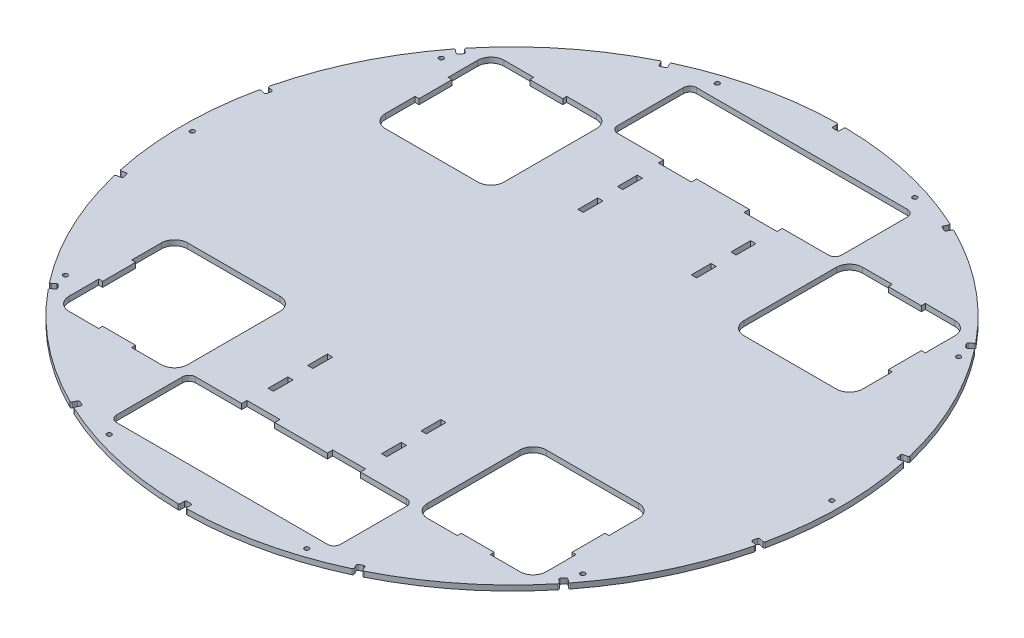
SolidWorks part; units mm, degrees
ref_plane "Front Plane" through (0, 0, 0) normal (0, 0, 1) x (1, 0, 0)
ref_plane "Top Plane" through (0, 0, 0) normal (0, 1, 0) x (1, 0, 0)
ref_plane "Right Plane" through (0, 0, 0) normal (1, 0, 0) x (0, 0, -1)
sketch "Sketch1" plane through (0, 0, 0) normal (0, 1, 0) x (1, 0, 0)
  circle A0 centre (0, 0) radius 250
extrude "Boss-Extrude1" add sketch "Sketch1" along normal blind 4
sketch "Sketch2" plane through (0, 4, 0) normal (0, 1, 0) x (1, 0, 0)
  line L0 (0, -250) -> (0, 250) construction
  line L1 (80, 220) -> (-80, 220)
  line L2 (85, 215) -> (85, 165)
  line L3 (80, 160) -> (-80, 160)
  line L4 (-85, 215) -> (-85, 165)
  line L5 (85, 220) -> (-85, 160) construction
  line L6 (85, 160) -> (-85, 220) construction
  line L7 (-55, 0) -> (55, 0) construction
  line L8 (85, -215) -> (85, -165)
  line L9 (80, -160) -> (-80, -160)
  line L10 (-85, -215) -> (-85, -165)
  line L11 (80, -220) -> (-80, -220)
  circle A0 centre (0, 0) radius 250 construction
  arc A1 (-80, 160) -> (-85, 165) centre (-80, 165) cw
  arc A2 (80, 160) -> (85, 165) centre (80, 165) ccw
  arc A3 (85, 215) -> (80, 220) centre (80, 215) ccw
  arc A4 (-80, 220) -> (-85, 215) centre (-80, 215) ccw
  arc A5 (-85, -215) -> (-80, -220) centre (-80, -215) ccw
  arc A6 (80, -220) -> (85, -215) centre (80, -215) ccw
  arc A7 (85, -165) -> (80, -160) centre (80, -165) ccw
  arc A8 (-80, -160) -> (-85, -165) centre (-80, -165) ccw
  point P0 (0, 190)
  point P33 (-85, -220)
  point P36 (85, -220)
  point P39 (85, -160)
  point P42 (-85, -160)
  dimension "D4" = 5
  dimension "D5" = 5
  dimension "D1" = 170
  dimension "D2" = 190
  dimension "D3" = 60
extrude "Cut-Extrude1" cut sketch "Sketch2" against normal blind 10
sketch "Sketch3" plane through (0, 4, 0) normal (0, 1, 0) x (1, 0, 0)
  line L0 (45, 160) -> (-45, 160)
  line L1 (-80, 160) -> (80, 160) construction
  line L2 (0, -2.2) -> (0, 2.2) construction
  line L3 (-45, 160) -> (-20, 160)
  line L4 (-45, 160) -> (-45, 156)
  line L5 (-45, 156) -> (-20, 156)
  line L6 (-20, 160) -> (-20, 156)
  line L7 (20, 160) -> (20, 156)
  line L8 (45, 156) -> (20, 156)
  line L9 (45, 160) -> (45, 156)
  line L10 (45, 160) -> (20, 160)
  line L11 (-2.2, 0) -> (2.2, 0) construction
  line L12 (45, -160) -> (20, -160)
  line L13 (45, -160) -> (45, -156)
  line L14 (45, -156) -> (20, -156)
  line L15 (20, -160) -> (20, -156)
  line L16 (-20, -160) -> (-20, -156)
  line L17 (-45, -156) -> (-20, -156)
  line L18 (-45, -160) -> (-45, -156)
  line L19 (-45, -160) -> (-20, -160)
  line L20 (45, -160) -> (-45, -160)
  point P5 (0, 160)
  point P24 (0, -160)
  line M7 (80, 160) -> (-80, 160)
  line M10 (-80, -160) -> (80, -160)
  dimension "D2" = 4
  dimension "D3" = 25
extrude "Cut-Extrude2" cut sketch "Sketch3" against normal blind 5 contours L6 L0 L4 L5 | L9 L7 L8 M7 | L18 L16 L17 M10 | L15 L13 L14 M10 region at (32.5, 4, -158) region at (-32.5, 4, -158) region at (-32.5, 4, 158) region at (32.5, 4, 158)
sketch "Sketch4" plane through (0, 4, 0) normal (0, 1, 0) x (1, 0, 0)
  line L0 (45, 160) -> (-45, 160)
  line L3 (80, 220) -> (-80, 220) construction
  line L4 (45, 160) -> (80, 160) construction
  line L5 (45, 140) -> (41, 140)
  line L6 (45, 140) -> (45, 125)
  line L7 (45, 125) -> (41, 125)
  line L8 (41, 140) -> (41, 125)
  line L9 (0, -2.2) -> (0, 2.2) construction
  line L10 (41, 110) -> (45, 110)
  line L11 (41, 110) -> (41, 95)
  line L12 (41, 95) -> (45, 95)
  line L13 (45, 110) -> (45, 95)
  line L14 (-45, 110) -> (-45, 95)
  line L15 (-41, 95) -> (-45, 95)
  line L16 (-41, 110) -> (-41, 95)
  line L17 (-41, 110) -> (-45, 110)
  line L18 (-41, 140) -> (-41, 125)
  line L19 (-45, 125) -> (-41, 125)
  line L20 (-45, 140) -> (-45, 125)
  line L21 (-45, 140) -> (-41, 140)
  line L22 (-2.2, 0) -> (2.2, 0) construction
  line L23 (-45, -140) -> (-41, -140)
  line L24 (-45, -140) -> (-45, -125)
  line L25 (-45, -125) -> (-41, -125)
  line L26 (-41, -140) -> (-41, -125)
  line L27 (-41, -110) -> (-45, -110)
  line L28 (-41, -110) -> (-41, -95)
  line L29 (-41, -95) -> (-45, -95)
  line L30 (-45, -110) -> (-45, -95)
  line L31 (45, -110) -> (45, -95)
  line L32 (41, -95) -> (45, -95)
  line L33 (41, -110) -> (41, -95)
  line L34 (41, -110) -> (45, -110)
  line L35 (41, -140) -> (41, -125)
  line L36 (45, -125) -> (41, -125)
  line L37 (45, -140) -> (45, -125)
  line L38 (45, -140) -> (41, -140)
  point P3 (0, 160)
  point P5 (0, 220)
  point P16 (45, 132.5)
  point P17 (45, 102.5)
  dimension "D1" = 0
  dimension "D2" = 4
  dimension "D3" = 0
  dimension "D4" = 90
  dimension "D5" = 15
  dimension "D6" = 20
  dimension "D7" = 15
  dimension "D8" = 4
  dimension "D9" = 30
extrude "Cut-Extrude3" cut sketch "Sketch4" against normal blind 20 contours L5 L8 L7 L6 | L13 L10 L11 L12 | L21 L20 L19 L18 | L16 L17 L14 L15 | L30 L27 L28 L29 | L23 L26 L25 L24 | L33 L34 L31 L32 | L38 L37 L36 L35 region at (43, 4, -132.5) region at (43, 4, -102.5) region at (-43, 4, -102.5) region at (-43, 4, -132.5) region at (-43, 4, 132.5) region at (-43, 4, 102.5) region at (43, 4, 102.5) region at (43, 4, 132.5)
sketch "Sketch7" plane through (0, 4, 0) normal (0, 1, 0) x (1, 0, 0)
  line L0 (0, -2.2) -> (0, 2.2) construction
  line L1 (-101, 75) -> (-171, 75)
  line L2 (-91, 85) -> (-91, 155)
  line L3 (-101, 165) -> (-171, 165)
  line L4 (-181, 85) -> (-181, 155)
  line L5 (-91, 75) -> (-181, 165) construction
  line L6 (-91, 165) -> (-181, 75) construction
  line L7 (91, 165) -> (181, 75) construction
  line L8 (91, 75) -> (181, 165) construction
  line L9 (181, 85) -> (181, 155)
  line L10 (101, 165) -> (171, 165)
  line L11 (91, 85) -> (91, 155)
  line L12 (101, 75) -> (171, 75)
  line L13 (-2.2, 0) -> (2.2, 0) construction
  line L14 (91, -75) -> (181, -165) construction
  line L15 (91, -165) -> (181, -75) construction
  line L16 (101, -75) -> (171, -75)
  line L17 (91, -85) -> (91, -155)
  line L18 (101, -165) -> (171, -165)
  line L19 (181, -85) -> (181, -155)
  line L20 (-91, -165) -> (-181, -75) construction
  line L21 (-91, -75) -> (-181, -165) construction
  line L22 (-181, -85) -> (-181, -155)
  line L23 (-101, -165) -> (-171, -165)
  line L24 (-91, -85) -> (-91, -155)
  line L25 (-101, -75) -> (-171, -75)
  arc A0 (-171, 165) -> (-181, 155) centre (-171, 155) ccw
  arc A1 (-91, 155) -> (-101, 165) centre (-101, 155) ccw
  arc A2 (-181, -155) -> (-171, -165) centre (-171, -155) ccw
  arc A3 (-101, -165) -> (-91, -155) centre (-101, -155) ccw
  arc A4 (-91, -85) -> (-101, -75) centre (-101, -85) ccw
  arc A5 (-171, -75) -> (-181, -85) centre (-171, -85) ccw
  arc A6 (91, -155) -> (101, -165) centre (101, -155) ccw
  arc A7 (171, -165) -> (181, -155) centre (171, -155) ccw
  arc A8 (181, -85) -> (171, -75) centre (171, -85) ccw
  arc A9 (101, -75) -> (91, -85) centre (101, -85) ccw
  arc A10 (101, 75) -> (91, 85) centre (101, 85) cw
  arc A11 (171, 75) -> (181, 85) centre (171, 85) ccw
  arc A12 (181, 155) -> (171, 165) centre (171, 155) ccw
  arc A13 (91, 155) -> (101, 165) centre (101, 155) cw
  arc A14 (-171, 75) -> (-181, 85) centre (-171, 85) cw
  arc A15 (-101, 75) -> (-91, 85) centre (-101, 85) ccw
  point P0 (-136, 120)
  point P12 (136, 120)
  point P19 (136, -120)
  point P24 (-136, -120)
  dimension "D5" = 10
  dimension "D6" = 10
  dimension "D7" = 10
  dimension "D1" = 90
  dimension "D2" = 90
  dimension "D3" = 136
  dimension "D4" = 120
extrude "Cut-Extrude4" cut sketch "Sketch7" against normal blind 5
sketch "Sketch8" plane through (0, 4, 0) normal (0, 1, 0) x (1, 0, 0)
  line L0 (-181, 155) -> (-181, 85) construction
  line L1 (-178, 107.5) -> (-184, 107.5)
  line L2 (-178, 107.5) -> (-178, 132.5)
  line L3 (-178, 132.5) -> (-184, 132.5)
  line L4 (-184, 107.5) -> (-184, 132.5)
  line L5 (-178, 107.5) -> (-184, 132.5) construction
  line L6 (-178, 132.5) -> (-184, 107.5) construction
  line L7 (-101, 165) -> (-171, 165) construction
  line L8 (-123.5, 162) -> (-148.5, 162)
  line L9 (-123.5, 162) -> (-123.5, 168)
  line L10 (-123.5, 168) -> (-148.5, 168)
  line L11 (-148.5, 162) -> (-148.5, 168)
  line L12 (-123.5, 162) -> (-148.5, 168) construction
  line L13 (-123.5, 168) -> (-148.5, 162) construction
  line L14 (0, -2.2) -> (0, 2.2) construction
  line L15 (123.5, 168) -> (148.5, 162) construction
  line L16 (123.5, 162) -> (148.5, 168) construction
  line L17 (178, 132.5) -> (184, 107.5) construction
  line L18 (178, 107.5) -> (184, 132.5) construction
  line L19 (148.5, 162) -> (148.5, 168)
  line L20 (123.5, 168) -> (148.5, 168)
  line L21 (123.5, 162) -> (123.5, 168)
  line L22 (123.5, 162) -> (148.5, 162)
  line L23 (184, 107.5) -> (184, 132.5)
  line L24 (178, 132.5) -> (184, 132.5)
  line L25 (178, 107.5) -> (178, 132.5)
  line L26 (178, 107.5) -> (184, 107.5)
  line L27 (-2.2, 0) -> (2.2, 0) construction
  line L28 (178, -107.5) -> (184, -132.5) construction
  line L29 (178, -132.5) -> (184, -107.5) construction
  line L30 (123.5, -162) -> (148.5, -168) construction
  line L31 (123.5, -168) -> (148.5, -162) construction
  line L32 (178, -107.5) -> (184, -107.5)
  line L33 (178, -107.5) -> (178, -132.5)
  line L34 (178, -132.5) -> (184, -132.5)
  line L35 (184, -107.5) -> (184, -132.5)
  line L36 (123.5, -162) -> (148.5, -162)
  line L37 (123.5, -162) -> (123.5, -168)
  line L38 (123.5, -168) -> (148.5, -168)
  line L39 (148.5, -162) -> (148.5, -168)
  line L40 (-123.5, -168) -> (-148.5, -162) construction
  line L41 (-123.5, -162) -> (-148.5, -168) construction
  line L42 (-178, -132.5) -> (-184, -107.5) construction
  line L43 (-178, -107.5) -> (-184, -132.5) construction
  line L44 (-148.5, -162) -> (-148.5, -168)
  line L45 (-123.5, -168) -> (-148.5, -168)
  line L46 (-123.5, -162) -> (-123.5, -168)
  line L47 (-123.5, -162) -> (-148.5, -162)
  line L48 (-184, -107.5) -> (-184, -132.5)
  line L49 (-178, -132.5) -> (-184, -132.5)
  line L50 (-178, -107.5) -> (-178, -132.5)
  line L51 (-178, -107.5) -> (-184, -107.5)
  point P0 (-181, 120)
  point P7 (-136, 165)
  point P24 (136, 165)
  point P25 (181, 120)
  point P36 (181, -120)
  point P37 (136, -165)
  point P46 (-136, -165)
  point P47 (-181, -120)
  dimension "D1" = 6
  dimension "D2" = 25
  dimension "D3" = 6
  dimension "D4" = 25
extrude "Boss-Extrude2" add sketch "Sketch8" against normal blind 4
sketch "Sketch11" plane through (0, 4, 0) normal (0, 1, 0) x (1, 0, 0)
  line L1 (1.5, 245) -> (-1.5, 245)
  line L2 (2.5, 246) -> (2.5, 255)
  line L3 (2.5, 255) -> (-2.5, 255)
  line L4 (-2.5, 246) -> (-2.5, 255)
  line L5 (2.5, 245) -> (-2.5, 255) construction
  line L6 (2.5, 255) -> (-2.5, 245) construction
  circle A0 centre (0, 0) radius 250 construction
  arc A1 (2.5, 246) -> (1.5, 245) centre (1.5, 246) cw
  arc A2 (-1.5, 245) -> (-2.5, 246) centre (-1.5, 246) cw
  point P0 (0, 250)
  dimension "D3" = 1
  dimension "D1" = 10
  dimension "D2" = 5
extrude "Cut-Extrude5" cut sketch "Sketch11" against normal blind 4
fillet "Fillet1" radius 1 2 edges at (2.5, 2, -249.9875) (-2.5, 2, -249.9875)
pattern_circular "CirPattern1" count 14 over 360 about axis through (0, 4, 0) along (0, -1, 0) of "Cut-Extrude5", "Fillet1"
sketch "Sketch12" plane through (0, 4, 0) normal (0, 1, 0) x (1, 0, 0)
  circle A1 centre (0, 0) radius 242.5
  circle A3 centre (-242.5, 0) radius 1.7
  dimension "D2" = 485
extrude "Cut-Extrude6" cut sketch "Sketch12" against normal blind 10 contours A1 A3 | A1 A3 region at (-241.7774, 4, 0) region at (-243.2204, 4, 0)
pattern_circular "CirPattern2" count 10 over 360 about axis through (0, 4, 0) along (0, -1, 0) of "Cut-Extrude6" reverse direction yes
